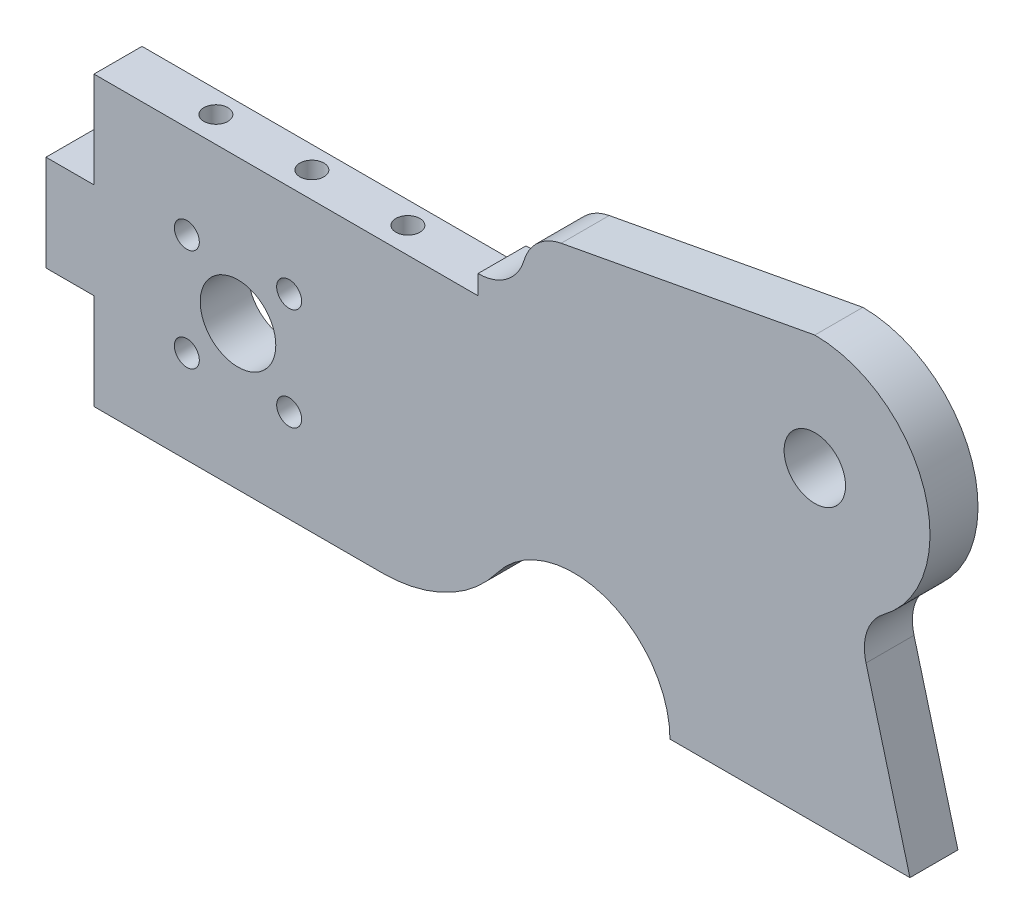
SolidWorks part; units mm, degrees
ref_plane "Front Plane" through (0, 0, 0) normal (0, 0, 1) x (1, 0, 0)
ref_plane "Top Plane" through (0, 0, 0) normal (0, 1, 0) x (1, 0, 0)
ref_plane "Right Plane" through (0, 0, 0) normal (1, 0, 0) x (0, 0, -1)
sketch "Sketch1" plane through (0, 0, 0) normal (0, 0, 1) x (1, 0, 0)
  line L0 (0, 0) -> (107.95, 0)
  line L3 (0, 38.1) -> (0, 25.4)
  line L4 (95.3675, 55.88) -> (0, 38.1)
  line L5 (0, 19.05) -> (100.2273, 19.05) construction
  line L6 (19.05, 19.05) -> (19.05, 28.62) construction
  line L7 (19.05, 19.05) -> (25.817, 25.817) construction
  line L8 (107.95, 0) -> (100.9363, 26.1756)
  line L10 (0, 12.7) -> (0, 0)
  line L11 (0, 25.4) -> (-6.35, 25.4)
  line L13 (0, 12.7) -> (-6.35, 12.7)
  line L14 (-6.35, 25.4) -> (-6.35, 12.7)
  line L15 (100.9363, 26.1756) -> (100.8688, 26.4276)
  arc A0 (100.8688, 26.4276) -> (95.3675, 55.88) centre (95.3675, 40.64) ccw
  circle A1 centre (95.3675, 40.64) radius 4.064
  circle A2 centre (19.05, 19.05) radius 9.57 construction
  circle A3 centre (25.817, 25.817) radius 1.651
  circle A4 centre (25.817, 12.283) radius 1.651
  circle A5 centre (12.283, 12.283) radius 1.651
  circle A6 centre (12.283, 25.817) radius 1.651
  point P26 (19.05, 19.05)
  dimension "D1" = 8.128
  dimension "D5" = 15.24
  dimension "D4" = 19.14
  dimension "D7" = 3.302
  dimension "D11" = 97.0107
  dimension "D2" = 38.1
  dimension "D3" = 40.64
  dimension "D6" = 107.95
  dimension "D8" = 45
  dimension "D9" = 4
  dimension "D10" = 19.05
  dimension "D12" = 75
  dimension "D14" = 12.7
  dimension "D15" = 12.7
  dimension "D16" = 6.35
extrude "Boss-Extrude1" add sketch "Sketch1" along normal blind 6.35
sketch "Sketch2" plane through (0, 0, 6.35) normal (0, 0, 1) x (1, 0, 0)
  circle A0 centre (95.3675, 40.64) radius 38.1 construction
sketch "Sketch3" plane through (0, 0, 0) normal (-1, 0, 0) x (0, 0, 1)
  line L0 (0, 38.1) -> (6.35, 25.4) construction
  line L1 (6.35, 12.7) -> (0, 0) construction
  circle A0 centre (3.175, 31.75) radius 1.5875
  circle A1 centre (3.175, 6.35) radius 1.5875
  dimension "D1" = 3.175
  dimension "D2" = 3.175
extrude "Cut-Extrude1" cut sketch "Sketch3" against normal blind 6.35
sketch "Sketch6" plane through (0, 0, 6.35) normal (0, 0, 1) x (1, 0, 0)
  line L0 (0, 0) -> (107.95, 0) construction
  line L1 (50.8, 0) -> (76.2, 0)
  arc A0 (76.2, 0) -> (50.8, 0) centre (63.5, 0) ccw
  dimension "D1" = 25.4
  dimension "D2" = 31.75
extrude "Cut-Extrude2" cut sketch "Sketch6" against normal blind 6.35
sketch "Sketch7" plane through (0, 0, 6.35) normal (0, 0, 1) x (1, 0, 0)
  line L0 (12.283, 25.817) -> (25.817, 12.283) construction
  line L1 (12.283, 12.283) -> (25.817, 25.817) construction
  circle A0 centre (19.05, 19.05) radius 5
  dimension "D1" = 10
extrude "Cut-Extrude3" cut sketch "Sketch7" against normal through all
fillet "Fillet1" radius 6.35 1 edges at (100.8688, 26.4276, 3.175)
sketch "Sketch8" plane through (0, 0, 6.35) normal (0, 0, 1) x (1, 0, 0)
  line L1 (0, 38.1) -> (50.8, 38.1)
  line L2 (0, 38.1) -> (0, 50.8)
  line L3 (0, 50.8) -> (50.8, 50.8)
  line L4 (50.8, 38.1) -> (50.8, 50.8)
  dimension "D1" = 50.8
  dimension "D2" = 12.7
extrude "Cut-Extrude4" cut sketch "Sketch8" against normal blind 50.8
sketch "Sketch9" plane through (0, 0, 6.35) normal (0, 0, 1) x (1, 0, 0)
  line L3 (50.8, 40.64) -> (57.15, 40.64)
  line L5 (57.15, 40.64) -> (50.8, 40.64)
  line L6 (57.15, 40.64) -> (57.15, 50.8)
  line L7 (57.15, 50.8) -> (50.8, 50.8)
  line L8 (50.8, 40.64) -> (50.8, 50.8)
  line L9 (0, 38.1) -> (50.8, 38.1) construction
  line M8 (50.8, 47.571) -> (50.8, 38.1)
  line M21 (95.3675, 55.88) -> (50.8, 47.571)
  dimension "D1" = 10.16
  dimension "D2" = 2.54
  dimension "D3" = 6.35
extrude "Cut-Extrude5" cut sketch "Sketch9" against normal blind 19.304 contours L3 L6 M21 M8 region at (54.0583, 44.4092, 6.35)
fillet "Fillet6" radius 6.35 1 edges at (57.15, 40.64, 3.175)
fillet "Fillet7" radius 6.35 1 edges at (57.15, 48.7549, 3.175)
fillet "Fillet8" radius 19.05 1 edges at (50.8, 0, 3.175)
sketch "Sketch10" plane through (0, 0, 0) normal (0, -1, 0) x (1, 0, 0)
  line L0 (76.2, 6.35) -> (107.95, 6.35) construction
  line L1 (0, 6.35) -> (0, 0) construction
  line L2 (0, 6.35) -> (38.1, 6.35) construction
  line L3 (107.95, 6.35) -> (107.95, 0) construction
  line L4 (76.2, 0) -> (76.2, 6.35) construction
  circle A0 centre (97.79, 3.175) radius 1.5875
  circle A1 centre (86.36, 3.175) radius 1.5875
  circle A2 centre (31.75, 3.175) radius 1.5875
  circle A3 centre (12.7, 3.175) radius 1.5875
  point P10 (0, 0)
  point P11 (0, 0)
  point P12 (13.8866, 6.35)
  point P17 (0, 0)
  dimension "D1" = 3.175
  dimension "D2" = 3.175
  dimension "D3" = 3.175
  dimension "D4" = 3.175
  dimension "D5" = 12.7
  dimension "D6" = 19.05
  dimension "D7" = 10.16
  dimension "D8" = 10.16
  dimension "D9" = 11.43
  dimension "D10" = 3.175
  dimension "D11" = 3.175
extrude "Cut-Extrude6" cut sketch "Sketch10" against normal blind 6.35
sketch "Sketch11" plane through (0, 38.1, 0) normal (0, 1, 0) x (1, 0, 0)
  line L0 (0, -6.35) -> (0, 0) construction
  line L1 (50.8, 0) -> (50.8, -6.35) construction
  line L2 (0, -6.35) -> (50.8, -6.35) construction
  circle A0 centre (12.7, -2.9224) radius 1.5875
  circle A1 centre (25.4, -2.9224) radius 1.5875
  circle A2 centre (38.1, -2.9224) radius 1.5875
  point P12 (12.7, -2.9224)
  dimension "D1" = 3.175
  dimension "D2" = 3.175
  dimension "D3" = 3.175
  dimension "D4" = 12.7
  dimension "D5" = 12.7
  dimension "D6" = 12.7
  dimension "D7" = 12.7
  dimension "D8" = 3.4276
extrude "Cut-Extrude7" cut sketch "Sketch11" against normal blind 6.35
